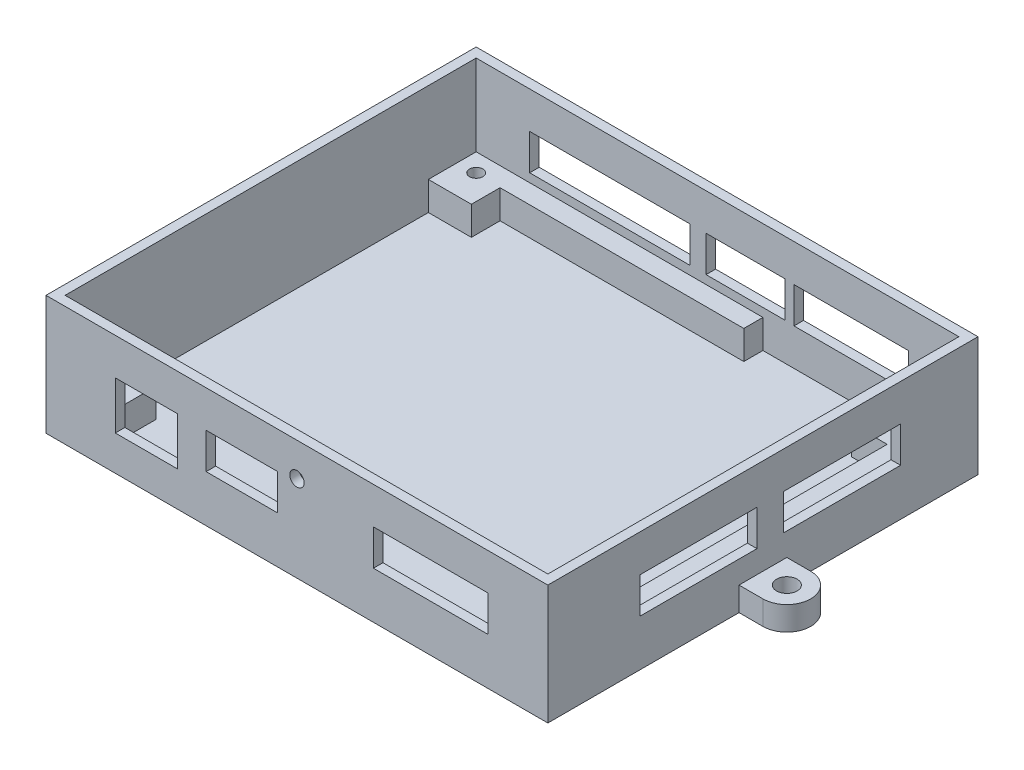
SolidWorks part; units mm, degrees
ref_plane "前视基准面" through (0, 0, 0) normal (0, 0, 1) x (1, 0, 0)
ref_plane "上视基准面" through (0, 0, 0) normal (0, 1, 0) x (1, 0, 0)
ref_plane "右视基准面" through (0, 0, 0) normal (1, 0, 0) x (0, 0, -1)
sketch "草图1" plane through (0, 0, 0) normal (0, 1, 0) x (1, 0, 0)
  line L0 (52.5, 45) -> (-52.5, 45)
  line L1 (50.5, -43) -> (-50.5, -43) construction
  line L2 (50.5, -43) -> (50.5, 43) construction
  line L3 (50.5, 43) -> (-50.5, 43) construction
  line L4 (-50.5, -43) -> (-50.5, 43) construction
  line L5 (50.5, -43) -> (-50.5, 43) construction
  line L6 (50.5, 43) -> (-50.5, -43) construction
  line L7 (-52.5, -45) -> (-52.5, 45)
  line L8 (52.5, -45) -> (-52.5, -45)
  line L9 (52.5, -45) -> (52.5, 45)
  point P0 (0, 0)
  dimension "D1" = 86
  dimension "D2" = 101
  dimension "D3" = 2
extrude "凸台-拉伸1" add sketch "草图1" along normal blind 25
shell "抽壳1" thickness 2 removed face at (0, 25, 0)
sketch "草图2" plane through (0, 2, 0) normal (0, 1, 0) x (1, 0, 0)
  line L0 (-41.5, 39) -> (-41.5, 33)
  line L1 (50.5, 43) -> (-50.5, 43) construction
  line L2 (-50.5, -43) -> (50.5, -43) construction
  line L3 (-41.5, -43) -> (-50.5, -43)
  line L4 (-50.5, -43) -> (-50.5, 43)
  line L5 (-50.5, 43) -> (-41.5, 43)
  line L6 (-41.5, -33) -> (-50.5, -33)
  line L7 (-41.5, 33) -> (-50.5, 33)
  line L8 (-50.5, 0) -> (50.5, 0) construction
  line L9 (50.5, -43) -> (50.5, 43) construction
  line L10 (-41.5, -33) -> (-41.5, -43)
  line L11 (50.5, 43) -> (50.5, -43)
  line L12 (-41.5, 43) -> (9.5, 43)
  line L13 (45.5, 33) -> (45.5, -32.46)
  line L14 (50.5, 43) -> (-50.5, 43) construction
  line L15 (43.96, -34) -> (42.04, -34)
  line L16 (45.5, 43) -> (50.5, 43)
  line L17 (45.5, 43) -> (38, 43)
  line L18 (-41.5, 39) -> (9.5, 39)
  line L19 (46.7, -39.2) -> (-46.7, -39.2) construction
  line L20 (46.7, -39.2) -> (46.7, 39.2) construction
  line L21 (46.7, 39.2) -> (-46.7, 39.2) construction
  line L22 (-46.7, -39.2) -> (-46.7, 39.2) construction
  line L23 (46.7, -39.2) -> (-46.7, 39.2) construction
  line L24 (46.7, 39.2) -> (-46.7, -39.2) construction
  line L25 (40.5, -35.54) -> (40.5, -43)
  line L26 (40.5, -43) -> (50.5, -43)
  line L27 (9.5, 43) -> (9.5, 39)
  line L28 (45.5, 43) -> (38, 43)
  line L30 (45.5, 33) -> (38, 33)
  line L31 (38, 43) -> (38, 33)
  circle A0 centre (46.6917, 39.1616) radius 1.4
  arc A1 (43.96, -34) -> (45.5, -32.46) centre (43.96, -32.46) ccw
  circle A2 centre (46.6879, -39.209) radius 1.4
  circle A3 centre (-46.6895, 39.1964) radius 1.4
  arc A4 (40.5, -35.54) -> (42.04, -34) centre (42.04, -35.54) cw
  circle A5 centre (-46.7251, -39.2209) radius 1.4
  point P35 (-41.5, 13.5)
  point P39 (9.5, 41)
  point P40 (0, 0)
  line M1 (50.5, -43) -> (50.5, 43)
  line M2 (50.5, 43) -> (-50.5, 43)
  line M3 (-50.5, 43) -> (-50.5, -43)
  line M4 (-50.5, -43) -> (50.5, -43)
  dimension "D7" = 1.54
  dimension "D9" = 2
  dimension "D12" = 10
  dimension "D13" = 12.5
  dimension "D2" = 51
  dimension "D4" = 5
  dimension "D5" = 9
  dimension "D6" = 10
  dimension "D10" = 93.4
  dimension "D11" = 78.4
sketch "草图3" plane through (0, 0, 45) normal (0, 0, 1) x (1, 0, 0)
  line L0 (-50.5, 2) -> (-50.5, 25) construction
  line L1 (-50.5, 2) -> (-41.5, 2) construction
  line L2 (-50.5, 25) -> (52.5, 25) construction
  line L3 (-50.5, 2) -> (50.5, 2) construction
  line L4 (40.5, 2) -> (50.5, 2) construction
  line L5 (50.5, 2) -> (50.5, 25) construction
  line L6 (50.5, 25) -> (-50.5, 25) construction
  line L7 (-50.5, 9.8) -> (50.5, 9.8) construction
  line L8 (40, 9.8) -> (40, 17.3)
  line L9 (16, 17.3) -> (40, 17.3)
  line L10 (16, 17.3) -> (16, 9.8)
  line L11 (16, 9.8) -> (40, 9.8)
  line L13 (-19, 9.8) -> (-4.1, 9.8)
  line L14 (-19, 9.8) -> (-19, 17.3)
  line L15 (-38, 17.3) -> (-25, 17.3)
  line L16 (-38, 17.3) -> (-38, 7.3)
  line L17 (-38, 7.3) -> (-25, 7.3)
  line L18 (-19, 17.3) -> (-4.1, 17.3)
  line L19 (-4.1, 17.3) -> (-4.1, 9.8)
  line L20 (-25, 17.3) -> (-25, 7.3)
  line L21 (-50.5, 8.1) -> (50.5, 8.1) construction
  line L23 (-4.1, 9.8) -> (-4.1, 8.1) construction
  dimension "D1" = 7.8
  dimension "D2" = 10.5
  dimension "D3" = 24
  dimension "D4" = 7.5
  dimension "D5" = 31.5
  dimension "D6" = 6.1
  dimension "D7" = 13
  dimension "D8" = 10
  dimension "D9" = 46.4
  dimension "D10" = 7.5
  dimension "D11" = 2.5
  dimension "D12" = 12.5
sketch "草图5" plane through (52.5, 0, 0) normal (1, 0, 0) x (0, 0, -1)
  line L0 (-43, 2) -> (43, 2) construction
  line L1 (-33, 2) -> (-43, 2) construction
  line L2 (-43, 2) -> (43, 2) construction
  line L3 (43, 2) -> (43, 25) construction
  line L4 (43, 25) -> (-43, 25) construction
  line L5 (-43, 25) -> (-43, 2) construction
  line L6 (-43, 8.1) -> (43, 8.1) construction
  line L7 (-43, 9.8) -> (43, 9.8) construction
  line L8 (28.8, 9.8) -> (4.3, 9.8)
  line L9 (28.8, 9.8) -> (28.8, 17.3)
  line L10 (4.3, 9.8) -> (4.3, 17.3)
  line L11 (28.8, 17.3) -> (4.3, 17.3)
  line L12 (-25.75, 9.7218) -> (-1.25, 9.7218)
  line L13 (-25.75, 9.7218) -> (-25.75, 17.2218)
  line L14 (-1.25, 9.7218) -> (-1.25, 17.2218)
  line L15 (-25.75, 17.2218) -> (-1.25, 17.2218)
  point P14 (28.8, 13.55)
  dimension "D8" = 17.25
  dimension "D1" = 6.1
  dimension "D2" = 7.8
  dimension "D3" = 24.5
  dimension "D4" = 7.5
  dimension "D5" = 14.2
  dimension "D6" = 24.5
  dimension "D7" = 7.5
  dimension "D9" = 0
sketch "草图7" plane through (0, 0, -45) normal (0, 0, -1) x (-1, 0, 0)
  line L0 (-50.5, 2) -> (-50.5, 25) construction
  line L1 (-40.5, 2) -> (-50.5, 2) construction
  line L2 (-50.5, 25) -> (50.5, 25) construction
  line L3 (50.5, 25) -> (50.5, 2) construction
  line L4 (50.5, 2) -> (41.5, 2) construction
  line L5 (50.5, 2) -> (-50.5, 2) construction
  line L6 (-50.5, 8.1) -> (50.5, 8.1) construction
  line L7 (-50.5, 9.8) -> (50.5, 9.8) construction
  line L9 (39.3, 9.8) -> (5.8, 9.8)
  line L10 (39.3, 9.8) -> (39.3, 17.3)
  line L11 (39.3, 17.3) -> (5.8, 17.3)
  line L12 (5.8, 9.8) -> (5.8, 17.3)
  line L13 (2.4, 9.8) -> (-14.1, 9.8)
  line L14 (2.4, 9.8) -> (2.4, 17.3)
  line L15 (2.4, 17.3) -> (-14.1, 17.3)
  line L16 (-14.1, 9.8) -> (-14.1, 17.3)
  line L17 (-40, 9.7026) -> (-16, 9.7026)
  line L18 (-40, 9.7026) -> (-40, 17.2026)
  line L19 (-40, 17.2026) -> (-16, 17.2026)
  line L20 (-16, 9.7026) -> (-16, 17.2026)
  point P18 (50.5, 13.5)
  dimension "D1" = 6.1
  dimension "D2" = 7.8
  dimension "D3" = 33.5
  dimension "D4" = 7.5
  dimension "D5" = 11.2
  dimension "D6" = 16.5
  dimension "D7" = 7.5
  dimension "D8" = 3.4
  dimension "D9" = 24
  dimension "D10" = 7.5
  dimension "D11" = 10.5
  dimension "D12" = 0
  dimension "D13" = 0
sketch "草图8" plane through (0, 0, 0) normal (0, -1, 0) x (1, 0, 0)
  line L0 (-52.5, -45) -> (-52.5, 45) construction
  line L1 (-40, 0) -> (52.5, 0) construction
  line L2 (52.5, 45) -> (52.5, -45) construction
  line L3 (-57.5, 5) -> (-52.5, 5)
  line L4 (-52.5, 5) -> (-52.5, -5)
  line L5 (-52.5, -5) -> (-57.5, -5)
  line L6 (0, 45) -> (0, -45) construction
  line L7 (-52.5, 45) -> (52.5, 45) construction
  line L8 (52.5, -45) -> (-52.5, -45) construction
  line L9 (52.5, -5) -> (57.5, -5)
  line L10 (52.5, 5) -> (52.5, -5)
  line L11 (57.5, 5) -> (52.5, 5)
  arc A0 (-57.5, 5) -> (-57.5, -5) centre (-57.5, 0) ccw
  circle A1 centre (-57.5, 0) radius 2.15
  circle A2 centre (57.5, 0) radius 2.15
  arc A3 (57.5, 5) -> (57.5, -5) centre (57.5, 0) cw
  point P2 (-52.5, 0)
  dimension "D1" = 10
  dimension "D3" = 4.3
  dimension "D2" = 5
extrude "凸台-拉伸3" add sketch "草图8" against normal blind 5
extrude "切除-拉伸2" cut sketch "草图3" against normal blind 10 contours L10 L11 L8 L9 | L19 L18 L14 L13 region at (28, 13.55, 45) region at (-11.55, 13.55, 45)
extrude "切除-拉伸3" cut sketch "草图5" against normal blind 10
extrude "切除-拉伸4" cut sketch "草图7" against normal blind 10
sketch "草图9" plane through (0, 0, 0) normal (0, 0, 1) x (1, 0, 0)
  circle A0 centre (0, 18) radius 1.5
extrude "切除-拉伸5" cut sketch "草图9" along normal blind 50
extrude "凸台-拉伸6" add sketch "草图2" along normal blind 6 contours L27 L7 L0 L18 A3 M2 M3 | A4 L25 L31 L30 L13 A1 L15 A2 A0 M4 M1 M2 | L10 L6 L4 A5 M4 region at (-24.7236, 2, -40.1006) region at (-45.9467, 2, 37.9103) region at (46.7438, 2, -2.0795)
extrude "切除-拉伸6" cut sketch "草图3<8>" against normal blind 10
sketch "草图3<8>" plane through (0, 0, 45) normal (0, 0, 1) x (1, 0, 0) same geometry as "草图3"
sketch "草图10" plane through (0, 0, 0) normal (0, 1, 0) x (1, 0, 0)
  line L1 (-66.5608, -48.0026) -> (73.4035, -48.0026)
  line L2 (-66.5608, -48.0026) -> (-66.5608, 51.1129)
  line L3 (-66.5608, 51.1129) -> (73.4035, 51.1129)
  line L4 (73.4035, -48.0026) -> (73.4035, 51.1129)
